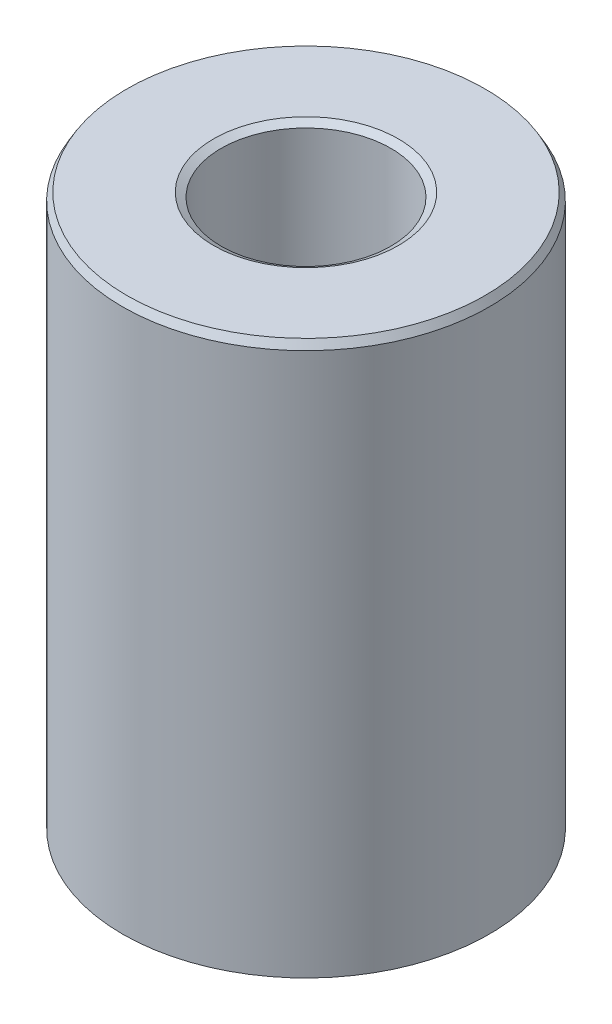
SolidWorks part; units mm, degrees
ref_plane "Front Plane" through (0, 0, 0) normal (0, 0, 1) x (1, 0, 0)
ref_plane "Top Plane" through (0, 0, 0) normal (0, 1, 0) x (1, 0, 0)
ref_plane "Right Plane" through (0, 0, 0) normal (1, 0, 0) x (0, 0, -1)
sketch "Sketch1" plane through (0, 0, 0) normal (0, 1, 0) x (1, 0, 0)
  circle A0 centre (0, 0) radius 12.5
  dimension "SLEEVE_OD" = 25
extrude "Boss-Extrude1" add sketch "Sketch1" along normal blind 37.8355
sketch "Sketch2" plane through (0, 0, 0) normal (0, 1, 0) x (1, 0, 0)
  circle A0 centre (0, 0) radius 5.7837
  dimension "BORE_D" = 11.5675
extrude "Cut-Extrude1" cut sketch "Sketch2" along normal through all
chamfer "Chamfer1" distance 0.5163 angle 30 4 edges at (0, 37.8355, 5.7837) (0, 0, 5.7837) (0, 0, 12.5) (0, 37.8355, 12.5) first distance on face at (0, 37.8355, 5.7837) first distance on face at (0, 0, 5.7837) first distance on face at (0, 37.8355, 12.5)
